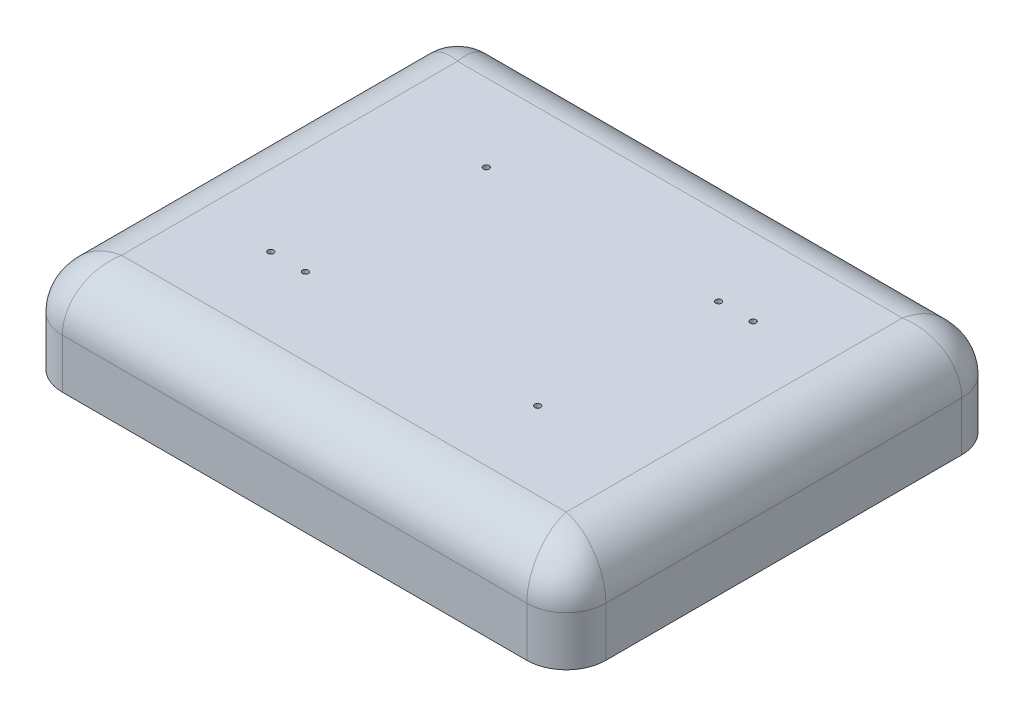
SolidWorks part; units mm, degrees
ref_plane "Alzado" through (0, 0, 0) normal (0, 0, 1) x (1, 0, 0)
ref_plane "Planta" through (0, 0, 0) normal (0, 1, 0) x (1, 0, 0)
ref_plane "Vista lateral" through (0, 0, 0) normal (1, 0, 0) x (0, 0, -1)
sketch "Croquis1" plane through (0, 0, 0) normal (0, 1, 0) x (1, 0, 0)
  line L1 (-117.5, 110) -> (117.5, 110)
  line L2 (-137.5, 90) -> (-137.5, -90)
  line L3 (-117.5, -110) -> (117.5, -110)
  line L4 (137.5, 90) -> (137.5, -90)
  line L5 (-137.5, 110) -> (137.5, -110) construction
  line L6 (-137.5, -110) -> (137.5, 110) construction
  arc A0 (-137.5, -90) -> (-117.5, -110) centre (-117.5, -90) ccw
  arc A1 (117.5, -110) -> (137.5, -90) centre (117.5, -90) ccw
  arc A2 (117.5, 110) -> (137.5, 90) centre (117.5, 90) cw
  arc A3 (-117.5, 110) -> (-137.5, 90) centre (-117.5, 90) ccw
  point P0 (0, 0)
  dimension "D3" = 20
  dimension "D1" = 275
  dimension "D2" = 220
extrude "Saliente-Extruir1" add sketch "Croquis1" along normal mid plane 50
fillet "Redondeo1" radius 25 8 edges at (-131.6421, 25, 104.1421) (-137.5, 25, 0) (-131.6421, 25, -104.1421) (0, 25, -110) (131.6421, 25, -104.1421) (137.5, 25, 0) (131.6421, 25, 104.1421) (0, 25, 110)
sketch "Croquis2" plane through (0, 0, 0) normal (0, 1, 0) x (1, 0, 0)
  line L0 (-58.75, 0) -> (58.75, 0) construction
  line L1 (-58.75, 45.75) -> (-58.75, -45.75) construction
  line L2 (58.75, 45.75) -> (58.75, -45.75) construction
  line L3 (58.75, 45.75) -> (76.25, 45.75) construction
  line L4 (112.5, 85) -> (-112.5, 85)
  line L5 (-112.5, 85) -> (-112.5, -85)
  line L6 (-112.5, -85) -> (112.5, -85)
  line L7 (112.5, -85) -> (112.5, 85)
  line L8 (112.5, 85) -> (-112.5, 85) construction
  line L9 (-112.5, 85) -> (-112.5, -85) construction
  line L10 (-112.5, -85) -> (112.5, -85) construction
  line L11 (112.5, -85) -> (112.5, 85) construction
  line L12 (-58.75, -45.75) -> (-76.25, -45.75) construction
  circle A0 centre (-58.75, 45.75) radius 1.5
  circle A1 centre (58.75, 45.75) radius 1.5
  circle A2 centre (58.75, -45.75) radius 1.5
  circle A3 centre (-58.75, -45.75) radius 1.5
  circle A4 centre (76.25, 45.75) radius 1.5
  circle A5 centre (-76.25, -45.75) radius 1.5
  dimension "D2" = 3
  dimension "D3" = 117.5
  dimension "D4" = 91.5
  dimension "D5" = 17.5
  dimension "D6" = 17.5
  dimension "D1" = 0
extrude "Cortar-Extruir1" cut sketch "Croquis2" against normal blind 7 from surface starting at face at (0, 25, 0)
